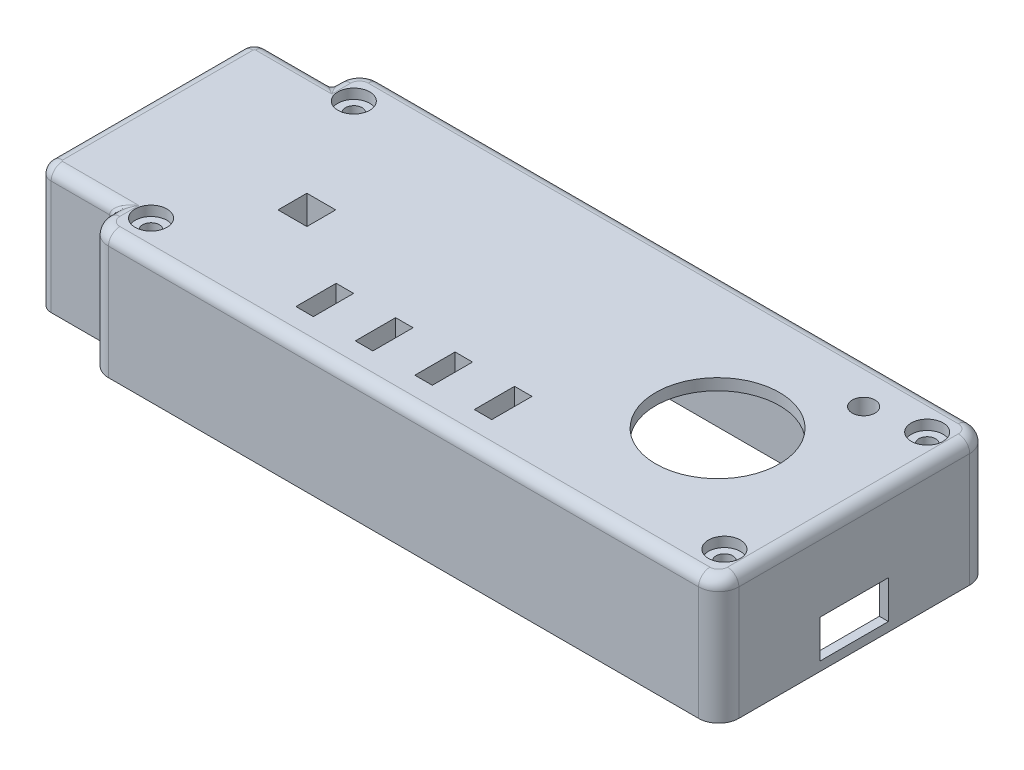
SolidWorks part; units mm, degrees
ref_plane "前视基准面" through (0, 0, 0) normal (0, 0, 1) x (1, 0, 0)
ref_plane "上视基准面" through (0, 0, 0) normal (0, 1, 0) x (1, 0, 0)
ref_plane "右视基准面" through (0, 0, 0) normal (1, 0, 0) x (0, 0, -1)
sketch "草图1" plane through (0, 0, 0) normal (0, 1, 0) x (1, 0, 0)
  line L0 (-34.2494, -15.8507) -> (43.4506, -15.8507) construction
  line L1 (-35.3994, -14.7007) -> (-35.3994, -13.3507) construction
  line L2 (-34.2494, 16.8493) -> (43.4506, 16.8493) construction
  line L3 (44.6006, -14.7007) -> (44.6006, 15.6993) construction
  line L4 (-36.5494, -12.2007) -> (-44.4494, -12.2007) construction
  line L5 (-45.5994, -11.0507) -> (-45.5994, 12.0493) construction
  line L6 (-44.4494, 13.1993) -> (-36.5494, 13.1993) construction
  line L7 (-35.3994, 14.3493) -> (-35.3994, 15.6993) construction
  line L8 (-34.2494, -16.1507) -> (43.4506, -16.1507)
  line L9 (44.9006, -14.7007) -> (44.9006, 15.6993)
  line L10 (-34.2494, 17.1493) -> (43.4506, 17.1493)
  line L11 (-35.6994, 14.3493) -> (-35.6994, 15.6993)
  line L12 (-44.4494, 13.4993) -> (-36.5494, 13.4993)
  line L13 (-45.8994, -11.0507) -> (-45.8994, 12.0493)
  line L14 (-36.5494, -12.5007) -> (-44.4494, -12.5007)
  line L15 (-35.6994, -14.7007) -> (-35.6994, -13.3507)
  line L16 (-47.0994, -11.0507) -> (-47.0994, 12.0493)
  line L17 (-44.4494, 14.6993) -> (-36.8994, 14.6993)
  line L18 (-36.8994, 14.6993) -> (-36.8994, 15.6993)
  line L19 (-34.2494, 18.3493) -> (43.4506, 18.3493)
  line L20 (46.1006, -14.7007) -> (46.1006, 15.6993)
  line L21 (-34.2494, -17.3507) -> (43.4506, -17.3507)
  line L22 (-36.8994, -14.7007) -> (-36.8994, -13.7007)
  line L23 (-36.8994, -13.7007) -> (-44.4494, -13.7007)
  line L24 (-47.0994, 12.0493) -> (-47.0994, 13.0493)
  line L25 (-44.4494, 14.6993) -> (-45.4494, 14.6993)
  line L26 (-44.4494, -13.7007) -> (-45.4494, -13.7007)
  line L27 (-47.0994, -11.0507) -> (-47.0994, -12.0507)
  arc A0 (44.6006, -14.7007) -> (43.4506, -15.8507) centre (43.4506, -14.7007) cw construction
  arc A1 (43.4506, 16.8493) -> (44.6006, 15.6993) centre (43.4506, 15.6993) cw construction
  arc A2 (-35.3994, -14.7007) -> (-34.2494, -15.8507) centre (-34.2494, -14.7007) ccw construction
  arc A3 (-36.5494, -12.2007) -> (-35.3994, -13.3507) centre (-36.5494, -13.3507) cw construction
  arc A4 (-45.5994, -11.0507) -> (-44.4494, -12.2007) centre (-44.4494, -11.0507) ccw construction
  arc A5 (-44.4494, 13.1993) -> (-45.5994, 12.0493) centre (-44.4494, 12.0493) ccw construction
  arc A6 (-35.3994, 14.3493) -> (-36.5494, 13.1993) centre (-36.5494, 14.3493) cw construction
  arc A7 (-35.3994, 15.6993) -> (-34.2494, 16.8493) centre (-34.2494, 15.6993) cw construction
  arc A8 (44.9006, -14.7007) -> (43.4506, -16.1507) centre (43.4506, -14.7007) cw
  arc A9 (43.4506, 17.1493) -> (44.9006, 15.6993) centre (43.4506, 15.6993) cw
  arc A10 (-35.6994, 15.6993) -> (-34.2494, 17.1493) centre (-34.2494, 15.6993) cw
  arc A11 (-35.6994, 14.3493) -> (-36.5494, 13.4993) centre (-36.5494, 14.3493) cw
  arc A12 (-44.4494, 13.4993) -> (-45.8994, 12.0493) centre (-44.4494, 12.0493) ccw
  arc A13 (-45.8994, -11.0507) -> (-44.4494, -12.5007) centre (-44.4494, -11.0507) ccw
  arc A14 (-36.5494, -12.5007) -> (-35.6994, -13.3507) centre (-36.5494, -13.3507) cw
  arc A15 (-35.6994, -14.7007) -> (-34.2494, -16.1507) centre (-34.2494, -14.7007) ccw
  arc A17 (-36.8994, 14.6993) -> (-36.8994, 14.6993) centre (-36.8994, 14.6993) cw
  arc A18 (-36.8994, 15.6993) -> (-34.2494, 18.3493) centre (-34.2494, 15.6993) cw
  arc A19 (43.4506, 18.3493) -> (46.1006, 15.6993) centre (43.4506, 15.6993) cw
  arc A20 (46.1006, -14.7007) -> (43.4506, -17.3507) centre (43.4506, -14.7007) cw
  arc A21 (-36.8994, -14.7007) -> (-34.2494, -17.3507) centre (-34.2494, -14.7007) ccw
  arc A22 (-36.8994, -13.7007) -> (-36.8994, -13.7007) centre (-36.8994, -13.7007) cw
  arc A24 (-44.4494, 14.6993) -> (-47.0994, 12.0493) centre (-44.4494, 12.0493) ccw construction
  arc A25 (-47.0994, -11.0507) -> (-44.4494, -13.7007) centre (-44.4494, -11.0507) ccw construction
  arc A26 (-47.0994, 13.0493) -> (-45.4494, 14.6993) centre (-45.4494, 13.0493) cw
  arc A27 (-45.4494, -13.7007) -> (-47.0994, -12.0507) centre (-45.4494, -12.0507) cw
  dimension "D4" = 1.45
  dimension "D1" = 0.3
  dimension "D2" = 90.8
  dimension "D3" = 33.3
  dimension "D7" = 1
  dimension "D5" = 1.2
extrude "凸台-拉伸1" add sketch "草图1" along normal blind 15
sketch "草图3" plane through (0, 15, 0) normal (0, 1, 0) x (1, 0, 0)
  line L0 (-47.0994, 13.0493) -> (-47.0994, -12.0507) construction
  line L1 (-36.8994, -13.7007) -> (-36.8994, -14.7007) construction
  line L2 (-45.4494, -13.7007) -> (-36.8994, -13.7007) construction
  line L3 (-34.2494, -17.3507) -> (43.4506, -17.3507) construction
  line L4 (46.1006, -14.7007) -> (46.1006, 15.6993) construction
  line L5 (43.4506, 18.3493) -> (-34.2494, 18.3493) construction
  line L6 (-36.8994, 14.6993) -> (-45.4494, 14.6993) construction
  line L7 (-47.0994, 13.0493) -> (-47.0994, -12.0507)
  line L8 (-36.8994, -13.7007) -> (-36.8994, -14.7007)
  line L9 (-45.4494, -13.7007) -> (-36.8994, -13.7007)
  line L10 (-34.2494, -17.3507) -> (43.4506, -17.3507)
  line L11 (46.1006, -14.7007) -> (46.1006, 15.6993)
  line L12 (43.4506, 18.3493) -> (-34.2494, 18.3493)
  line L13 (-36.8994, 14.6993) -> (-45.4494, 14.6993)
  line L14 (-36.8994, 15.6993) -> (-36.8994, 14.6993) construction
  line L15 (-36.8994, 15.6993) -> (-36.8994, 14.6993)
  arc A1 (-36.8994, -14.7007) -> (-34.2494, -17.3507) centre (-34.2494, -14.7007) ccw construction
  arc A2 (43.4506, -17.3507) -> (46.1006, -14.7007) centre (43.4506, -14.7007) ccw construction
  arc A3 (46.1006, 15.6993) -> (43.4506, 18.3493) centre (43.4506, 15.6993) ccw construction
  arc A4 (-34.2494, 18.3493) -> (-36.8994, 15.6993) centre (-34.2494, 15.6993) ccw construction
  arc A6 (-47.0994, -12.0507) -> (-45.4494, -13.7007) centre (-45.4494, -12.0507) ccw
  arc A7 (-36.8994, -14.7007) -> (-34.2494, -17.3507) centre (-34.2494, -14.7007) ccw
  arc A8 (43.4506, -17.3507) -> (46.1006, -14.7007) centre (43.4506, -14.7007) ccw
  arc A9 (46.1006, 15.6993) -> (43.4506, 18.3493) centre (43.4506, 15.6993) ccw
  arc A10 (-34.2494, 18.3493) -> (-36.8994, 15.6993) centre (-34.2494, 15.6993) ccw
  arc A11 (-45.4494, 14.6993) -> (-47.0994, 13.0493) centre (-45.4494, 13.0493) ccw
  arc A12 (-47.0994, -12.0507) -> (-45.4494, -13.7007) centre (-45.4494, -12.0507) ccw construction
  arc A13 (-45.4494, 14.6993) -> (-47.0994, 13.0493) centre (-45.4494, 13.0493) ccw construction
extrude "凸台-拉伸2" add sketch "草图3" along normal blind 1.5
fillet "圆角1" radius 1.5 14 edges at (-41.1744, 16.5, -14.6993) (-36.8994, 16.5, -15.1993) (-36.1233, 16.5, -17.5731) (4.6006, 16.5, -18.3493) (45.3244, 16.5, -17.5731) (46.1006, 16.5, -0.4993) (45.3244, 16.5, 16.5745) (4.6006, 16.5, 17.3507) (-36.1233, 16.5, 16.5745) (-36.8994, 16.5, 14.2007) (-41.1744, 16.5, 13.7007) (-46.6162, 16.5, 13.2174) (-47.0994, 16.5, -0.4993) (-46.6162, 16.5, -14.216)
sketch "草图4" plane through (0, 16.5, 0) normal (0, 1, 0) x (1, 0, 0)
  line L0 (-34.2494, 18.3493) -> (43.4506, 18.3493) construction
  line L1 (-36.8994, 14.6993) -> (-36.8994, 15.6993) construction
  line L2 (4.6006, -16.1507) -> (4.6006, 17.1493) construction
  line L3 (44.9006, -14.7007) -> (44.9006, 15.6993) construction
  line L4 (-34.2494, -16.1507) -> (43.4506, -16.1507) construction
  line L6 (44.9006, 0.4993) -> (4.6006, 0.4993) construction
  line L7 (43.4506, 17.1493) -> (-34.2494, 17.1493) construction
  circle A0 centre (-33.1494, 13.8493) radius 1.1
  circle A1 centre (-33.1494, 13.8493) radius 3.1
  circle A2 centre (42.3506, 13.8493) radius 1.1
  circle A3 centre (42.3506, 13.8493) radius 3.1
  circle A4 centre (-33.1494, -12.8507) radius 1.1
  circle A5 centre (-33.1494, -12.8507) radius 3.1
  circle A6 centre (42.3506, -12.8507) radius 1.1
  circle A7 centre (42.3506, -12.8507) radius 3.1
  dimension "D1" = 4.5
  dimension "D2" = 3.75
  dimension "D3" = 2.2
  dimension "D4" = 2
ref_plane "基准面1" through (0, 1.7, 0) normal (0, -1, 0) x (-1, 0, 0)
sketch "草图5" plane through (0, 1.7, 0) normal (0, -1, 0) x (-1, 0, 0)
  line L0 (32.1494, 16.7836) -> (32.1494, 17.1493)
  line L1 (-43.4506, 17.1493) -> (34.2494, 17.1493) construction
  line L2 (34.1494, 16.7836) -> (34.1494, 17.1493)
  line L3 (32.1494, 17.1493) -> (34.1494, 17.1493)
  line L4 (33.1494, 13.8493) -> (33.1494, 18.1906) construction
  line L5 (-4.6006, 17.1493) -> (-4.6006, -16.1507) construction
  line L6 (-4.6006, 0.4993) -> (-44.9006, 0.4993) construction
  line L7 (-41.3506, 16.7836) -> (-41.3506, 17.1493)
  line L8 (-41.3506, 17.1493) -> (-43.3506, 17.1493)
  line L9 (-43.3506, 16.7836) -> (-43.3506, 17.1493)
  line L10 (32.1494, -15.785) -> (32.1494, -16.1507)
  line L11 (32.1494, -16.1507) -> (34.1494, -16.1507)
  line L12 (34.1494, -15.785) -> (34.1494, -16.1507)
  line L13 (-43.3506, -15.785) -> (-43.3506, -16.1507)
  line L14 (-41.3506, -16.1507) -> (-43.3506, -16.1507)
  line L15 (-41.3506, -15.785) -> (-41.3506, -16.1507)
  circle A0 centre (33.1494, 13.8493) radius 1.1
  arc A1 (32.1494, 16.7836) -> (34.1494, 16.7836) centre (33.1494, 13.8493) ccw
  circle A2 centre (33.1494, 13.8493) radius 1.1 construction
  circle A3 centre (33.1494, 13.8493) radius 3.1 construction
  arc A4 (-41.3506, 16.7836) -> (-43.3506, 16.7836) centre (-42.3506, 13.8493) cw
  arc A5 (32.1494, -15.785) -> (34.1494, -15.785) centre (33.1494, -12.8507) cw
  arc A6 (-41.3506, -15.785) -> (-43.3506, -15.785) centre (-42.3506, -12.8507) ccw
  point P3 (32.1494, 16.9664)
  dimension "D1" = 2
extrude "凸台-拉伸3" add sketch "草图5" against normal up to next
sketch "草图6" plane through (0, 1.7, 0) normal (0, -1, 0) x (1, 0, 0)
  circle A0 centre (-33.1494, -13.8493) radius 1.1
  circle A1 centre (-33.1494, 12.8507) radius 1.1
  circle A2 centre (42.3506, 12.8507) radius 1.1
  circle A3 centre (42.3506, -13.8493) radius 1.1
extrude "切除-拉伸1" cut sketch "草图6" against normal through all
fillet "圆角2" radius 0.85 4 edges at (-36.4601, 16.0607, 13.2614) (-36.4601, 16.0607, -14.2599) (-36.8994, 7.5, 13.7007) (-36.8994, 7.5, -14.6993)
sketch "草图7" plane through (0, 16.5, 0) normal (0, 1, 0) x (1, 0, 0)
  circle A0 centre (-33.1494, 13.8493) radius 2.1
  circle A1 centre (42.3506, 13.8493) radius 2.1
  circle A2 centre (42.3506, -12.8507) radius 2.1
  circle A3 centre (-33.1494, -12.8507) radius 2.1
  dimension "D1" = 4.2
extrude "切除-拉伸2" cut sketch "草图7" against normal blind 1.3
sketch "草图8" plane through (0, 0, 0) normal (0, -1, 0) x (1, 0, 0)
  line L0 (-45.8994, 11.0507) -> (-45.8994, 12.5007)
  line L1 (-44.4494, 12.5007) -> (-45.8994, 12.5007)
  line L2 (-45.8994, 11.0507) -> (-44.4494, 11.0507)
  line L3 (-44.4494, 11.0507) -> (-44.4494, 12.5007)
  line L4 (-45.8994, -12.0493) -> (-45.8994, -13.4993)
  line L5 (-45.8994, -13.4993) -> (-44.4494, -13.4993)
  line L6 (-44.4494, -13.4993) -> (-44.4494, -12.0493)
  line L7 (-44.4494, -12.0493) -> (-45.8994, -12.0493)
extrude "切除-拉伸3" cut sketch "草图8" against normal up to surface (15 mm away) up to face at (-11.157, 15, -0.4993)
sketch "草图10" plane through (0, 16.5, 0) normal (0, 1, 0) x (1, 0, 0)
  line L0 (46.1006, 15.6993) -> (46.1006, -14.7007) construction
  line L5 (9.9596, -13.3937) -> (12.2596, -13.3937)
  line L6 (9.9596, -13.3937) -> (9.9596, -8.0937)
  line L7 (9.9596, -8.0937) -> (12.2596, -8.0937)
  line L8 (12.2596, -13.3937) -> (12.2596, -8.0937)
  line L9 (9.9596, -13.3937) -> (12.2596, -8.0937) construction
  line L10 (9.9596, -8.0937) -> (12.2596, -13.3937) construction
  line L11 (43.4506, -17.3507) -> (-34.2494, -17.3507) construction
  line L12 (2.1296, -13.3937) -> (2.1296, -8.0937)
  line L13 (2.1296, -13.3937) -> (4.4296, -13.3937)
  line L14 (4.4296, -13.3937) -> (4.4296, -8.0937)
  line L15 (2.1296, -8.0937) -> (4.4296, -8.0937)
  line L16 (-5.7004, -13.3937) -> (-5.7004, -8.0937)
  line L17 (-5.7004, -13.3937) -> (-3.4004, -13.3937)
  line L18 (-3.4004, -13.3937) -> (-3.4004, -8.0937)
  line L19 (-5.7004, -8.0937) -> (-3.4004, -8.0937)
  line L20 (-13.5304, -13.3937) -> (-13.5304, -8.0937)
  line L21 (-13.5304, -13.3937) -> (-11.2304, -13.3937)
  line L22 (-11.2304, -13.3937) -> (-11.2304, -8.0937)
  line L23 (-13.5304, -8.0937) -> (-11.2304, -8.0937)
  line L24 (46.1006, 0.4993) -> (-32.0326, 0.4993) construction
  line L25 (-47.0994, -12.0507) -> (-47.0994, 13.0493) construction
  line L26 (-34.2494, 18.3493) -> (43.4506, 18.3493) construction
  line L28 (-25.7294, 0.2493) -> (-21.9294, 0.2493)
  line L29 (-25.7294, 0.2493) -> (-25.7294, -3.5507)
  line L30 (-25.7294, -3.5507) -> (-21.9294, -3.5507)
  line L31 (-21.9294, 0.2493) -> (-21.9294, -3.5507)
  line L32 (-25.7294, 0.2493) -> (-21.9294, -3.5507) construction
  line L33 (-25.7294, -3.5507) -> (-21.9294, 0.2493) construction
  circle A0 centre (28.1006, 0.4993) radius 8.15
  circle A1 centre (-23.8294, -1.6507) radius 1.5 construction
  circle A2 centre (35.2506, 12.5793) radius 1.5
  point P0 (11.1096, -10.7437)
  dimension "D6" = 16.3
  dimension "D8" = 3
  dimension "D9" = 3
  dimension "D10" = 23.27
  dimension "D11" = 15.7
  dimension "D12" = 10.85
  dimension "D13" = 5.77
  dimension "D1" = 2.3
  dimension "D2" = 5.3
  dimension "D3" = 34.991
  dimension "D4" = 6.607
  dimension "D7" = 18
  dimension "D14" = 3.8
  dimension "D15" = 3.8
  dimension "D5" = 4
extrude "切除-拉伸5" cut sketch "草图10" against normal through all contours L15 L12 L13 L14 | L19 L16 L17 L18 | L23 L20 L21 L22 | L6 L5 L8 L7 | A0 | A1 | A2 | L29 L28 L31 L30 region at (3.2796, 16.5, 10.7437) region at (-4.5504, 16.5, 10.7437) region at (-12.3804, 16.5, 10.7437)
sketch "草图11" plane through (0, 15, 0) normal (0, -1, 0) x (1, 0, 0)
  line L0 (-14.5304, 7.0937) -> (-14.5304, 14.3937)
  line L1 (-13.5304, 8.0937) -> (-11.2304, 8.0937)
  line L2 (-13.5304, 8.0937) -> (-13.5304, 13.3937)
  line L3 (-13.5304, 13.3937) -> (-11.2304, 13.3937)
  line L4 (-11.2304, 8.0937) -> (-11.2304, 13.3937)
  line L5 (-14.5304, 14.3937) -> (-10.2304, 14.3937)
  line L6 (-10.2304, 7.0937) -> (-10.2304, 14.3937)
  line L7 (-14.5304, 7.0937) -> (-10.2304, 7.0937)
  line L8 (-6.7004, 7.0937) -> (-2.4004, 7.0937)
  line L9 (-5.7004, 8.0937) -> (-3.4004, 8.0937)
  line L10 (-5.7004, 8.0937) -> (-5.7004, 13.3937)
  line L11 (-5.7004, 13.3937) -> (-3.4004, 13.3937)
  line L12 (-3.4004, 8.0937) -> (-3.4004, 13.3937)
  line L13 (2.1296, 8.0937) -> (4.4296, 8.0937)
  line L14 (2.1296, 8.0937) -> (2.1296, 13.3937)
  line L15 (2.1296, 13.3937) -> (4.4296, 13.3937)
  line L16 (4.4296, 8.0937) -> (4.4296, 13.3937)
  line L17 (9.9596, 8.0937) -> (12.2596, 8.0937)
  line L18 (9.9596, 8.0937) -> (9.9596, 13.3937)
  line L19 (9.9596, 13.3937) -> (12.2596, 13.3937)
  line L20 (12.2596, 8.0937) -> (12.2596, 13.3937)
  line L21 (-2.4004, 7.0937) -> (-2.4004, 14.3937)
  line L22 (-6.7004, 14.3937) -> (-2.4004, 14.3937)
  line L23 (-6.7004, 7.0937) -> (-6.7004, 14.3937)
  line L24 (1.1296, 7.0937) -> (5.4296, 7.0937)
  line L25 (5.4296, 7.0937) -> (5.4296, 14.3937)
  line L26 (1.1296, 14.3937) -> (5.4296, 14.3937)
  line L27 (1.1296, 7.0937) -> (1.1296, 14.3937)
  line L28 (8.9596, 7.0937) -> (13.2596, 7.0937)
  line L29 (13.2596, 7.0937) -> (13.2596, 14.3937)
  line L30 (8.9596, 14.3937) -> (13.2596, 14.3937)
  line L31 (8.9596, 7.0937) -> (8.9596, 14.3937)
  dimension "D1" = 1
  dimension "D2" = 1
extrude "凸台-拉伸4" add sketch "草图11" along normal blind 2
sketch "草图12" plane through (46.1006, 0, 0) normal (1, 0, 0) x (0, 0, -1)
  line L1 (-4.0007, 1.2) -> (4.9993, 1.2)
  line L2 (-4.0007, 1.2) -> (-4.0007, 6.2)
  line L3 (-4.0007, 6.2) -> (4.9993, 6.2)
  line L4 (4.9993, 1.2) -> (4.9993, 6.2)
  line L5 (0.4993, 15) -> (0.4993, -3.739) construction
  line L6 (15.6993, 15) -> (-14.7007, 15) construction
  line L7 (-14.7007, 0) -> (15.6993, 0) construction
  dimension "D1" = 1.2
  dimension "D2" = 9
  dimension "D3" = 5
extrude "切除-拉伸6" cut sketch "草图12" against normal blind 10
sketch "草图13" plane through (0, 15, 0) normal (0, -1, 0) x (1, 0, 0)
  circle A0 centre (35.2506, -12.5793) radius 1.5
  circle A1 centre (35.2506, -12.5793) radius 3
  dimension "D1" = 1.5
extrude "凸台-拉伸5" add sketch "草图13" along normal blind 10.2
sketch "草图14" plane through (0, 15, 0) normal (0, -1, 0) x (1, 0, 0)
  line L11 (-21.9294, -0.2493) -> (-21.9294, 3.5507) construction
  line L12 (-25.7294, 3.5507) -> (-21.9294, 3.5507) construction
  line L13 (-25.7294, -0.2493) -> (-25.7294, 3.5507) construction
  line L14 (-25.7294, -0.2493) -> (-21.9294, -0.2493) construction
  line L15 (-27.2294, 5.0507) -> (-27.2294, -1.7493)
  line L16 (-20.4294, 5.0507) -> (-27.2294, 5.0507)
  line L17 (-20.4294, -1.7493) -> (-20.4294, 5.0507)
  line L18 (-27.2294, -1.7493) -> (-20.4294, -1.7493)
  line L19 (-27.2294, 5.0507) -> (-27.2294, -1.7493)
  line L20 (-20.4294, 5.0507) -> (-27.2294, 5.0507)
  line L21 (-20.4294, -1.7493) -> (-20.4294, 5.0507)
  line L22 (-27.2294, -1.7493) -> (-20.4294, -1.7493)
  line L23 (-21.9294, -0.2493) -> (-21.9294, 3.5507)
  line L24 (-25.7294, 3.5507) -> (-21.9294, 3.5507)
  line L25 (-25.7294, -0.2493) -> (-25.7294, 3.5507)
  line L26 (-25.7294, -0.2493) -> (-21.9294, -0.2493)
  dimension "D1" = 1.5
extrude "凸台-拉伸6" add sketch "草图14" along normal blind 7.8
